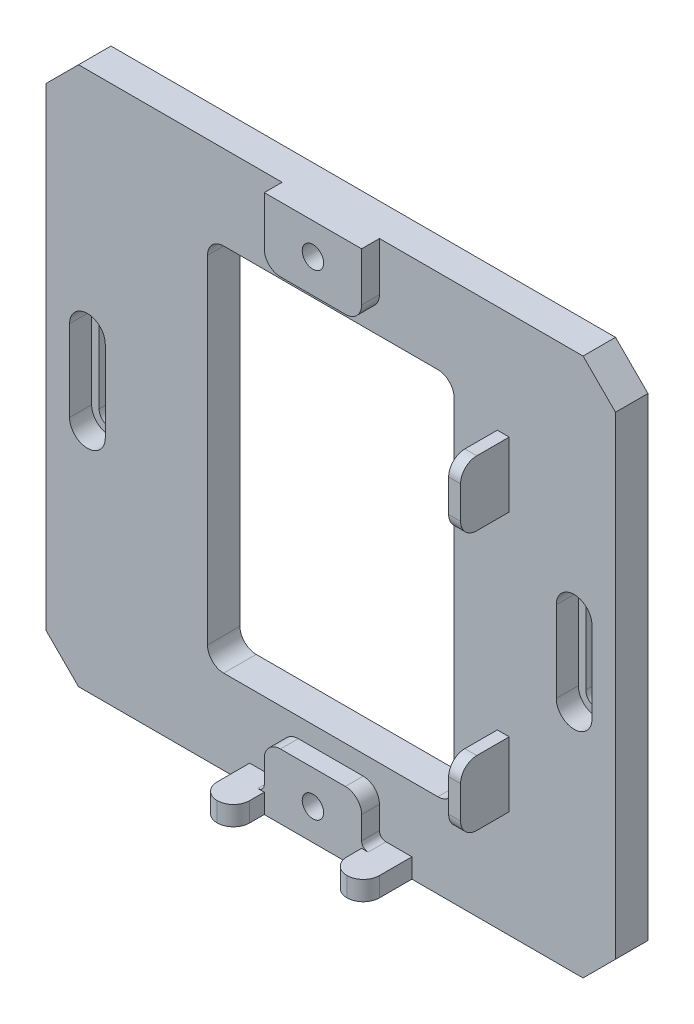
SolidWorks part; units mm, degrees
note: '?' marks a value the reader was unsure of.
material "6061 合金"
ref_plane "前视基准面" through (0, 0, 0) normal (0, 0, 1) x (1, 0, 0)
ref_plane "上视基准面" through (0, 0, 0) normal (0, 1, 0) x (1, 0, 0)
ref_plane "右视基准面" through (0, 0, 0) normal (1, 0, 0) x (0, 0, -1)
sketch "草图1" plane through (0, 0, 0) normal (0, 0, 1) x (1, 0, 0)
  line L0 (0, 0) -> (19.975, 0) construction
  line L1 (0, 0) -> (0, 23.7292) construction
  line L3 (-55, -83) -> (55, -83)
  line L4 (-55, -83) -> (-55, 83)
  line L5 (-55, 83) -> (55, 83)
  line L6 (55, -83) -> (55, 83)
  line L7 (-55, -83) -> (55, 83) construction
  line L8 (-55, 83) -> (55, -83) construction
  dimension "D1" = 110
  dimension "D2" = 166
extrude "凸台-拉伸1" add sketch "草图1" along normal blind 10
sketch "草图2" plane through (0, 0, 10) normal (0, 0, 1) x (1, 0, 0)
  line L0 (0, 0) -> (0, -83) construction
  line L1 (-55, -83) -> (55, -83) construction
  line L2 (0, 0) -> (30.9341, 0) construction
  line L3 (-15, -83) -> (15, -83)
  line L4 (-15, -83) -> (-15, -63)
  line L5 (-15, -63) -> (15, -63)
  line L6 (15, -83) -> (15, -63)
  line L7 (-15, 83) -> (-15, 63)
  line L8 (15, 83) -> (15, 63)
  line L9 (-15, 63) -> (15, 63)
  line L10 (-15, 83) -> (15, 83)
  dimension "D1" = 30
  dimension "D2" = 20
extrude "凸台-拉伸2" add sketch "草图2" along normal blind 5.5
sketch "草图3" plane through (0, 0, 0) normal (0, 0, -1) x (-1, 0, 0)
  line L0 (0, 0) -> (28.9291, 0) construction
  line L1 (0, 0) -> (0, -73.35) construction
  point P0 (0, -73.35)
  point P5 (0, 73.35)
  dimension "D1" = 146.7
hole_wizard "打孔尺寸(%根据)内六角圆柱头螺钉的类型2" positions "草图4" profile "草图5" counterbore size "M6" standard "GB" end condition through all
sketch "草图4" plane through (0, 0, 0) normal (0, 0, -1) x (-1, 0, 0)
  point P0 (0, -73.35)
  point P3 (0, 73.35)
sketch "草图5" plane through (0, -73.35, 0) normal (1, 0, 0) x (0, 1, 0)
  line L0 (0, 0) -> (0, 15.5)
  line L1 (0, 15.5) -> (3.3, 15.5)
  line L3 (3.3, 15.5) -> (3.3, 8.8)
  line L4 (3.3, 8.8) -> (5.5, 8.8)
  line L5 (5.5, 8.8) -> (5.5, 0)
  line L7 (5.5, 0) -> (0, 0)
  line L11 (0, -6.35) -> (0, 107.95) construction
  dimension "通孔孔直径" = 6.6
  dimension "通孔孔深度" = 15.5
  dimension "柱形沉头孔直径" = 11
  dimension "柱形沉头孔深度" = 8.8
sketch "草图6" plane through (0, 0, 10) normal (0, 0, 1) x (1, 0, 0)
  line L0 (-67, 0) -> (67, 0) construction
  line L1 (55, -83) -> (55, 83) construction
  line L2 (79, -10) -> (55, -10)
  line L3 (79, -10) -> (79, 10)
  line L4 (79, 10) -> (55, 10)
  line L5 (55, -10) -> (55, 10)
  line L6 (79, -10) -> (55, 10) construction
  line L7 (79, 10) -> (55, -10) construction
  line L9 (0, 0) -> (0, 19.4942) construction
  line L10 (-79, 10) -> (-55, -10) construction
  line L11 (-79, -10) -> (-55, 10) construction
  line L12 (-55, -10) -> (-55, 10)
  line L13 (-79, 10) -> (-55, 10)
  line L14 (-79, -10) -> (-79, 10)
  line L15 (-79, -10) -> (-55, -10)
  dimension "D1" = 24
  dimension "D2" = 20
extrude "凸台-拉伸3" [suppressed] add sketch "草图6" against normal blind 16.02
hole_wizard "M6 六角头螺钉的柱形沉头孔2" [suppressed] positions "草图7" profile "草图8" counterbore size "M6" standard "ANSI Metric"
sketch "草图7" plane through (0, 0, 10) normal (0, 0, 1) x (1, 0, 0)
  line L0 (0, 0) -> (0, 17.8301) construction
  point P0 (-63, 0)
  point P6 (63, 0)
sketch "草图8" plane through (-63, 0, 10) normal (1, 0, 0) x (0, -1, 0)
  line L0 (0, 0) -> (0, 10)
  line L1 (0, 10) -> (3.3, 10)
  line L3 (3.3, 10) -> (3.3, 4.15)
  line L4 (3.3, 4.15) -> (7.275, 4.15)
  line L5 (7.275, 4.15) -> (7.275, 0)
  line L7 (7.275, 0) -> (0, 0)
  line L11 (0, -6.35) -> (0, 107.95) construction
  dimension "通孔孔直径" = 6.6
  dimension "通孔孔深度" = 10
  dimension "柱形沉头孔直径" = 14.55
  dimension "柱形沉头孔深度" = 4.15
fillet "圆角1" [suppressed] radius 5
fillet "圆角2" radius 15 4 edges at (55, -83, 5) (-55, -83, 5) (55, 83, 5) (-55, 83, 5)
fillet "圆角3" radius 5 4 edges at (-15, 63, 12.75) (15, 63, 12.75) (15, -63, 12.75) (-15, -63, 12.75)
sketch "草图9" plane through (0, 0, 10) normal (0, 0, 1) x (1, 0, 0)
  line L1 (-38, -57) -> (38, -57)
  line L2 (-38, -57) -> (-38, 57)
  line L3 (-38, 57) -> (38, 57)
  line L4 (38, -57) -> (38, 57)
  line L5 (-38, -57) -> (38, 57) construction
  line L6 (-38, 57) -> (38, -57) construction
  point P0 (0, 0)
  dimension "D1" = 114
  dimension "D2" = 76
extrude "切除-拉伸1" cut sketch "草图9" against normal through all
fillet "圆角4" radius 5 4 edges at (38, -57, 5) (-38, -57, 5) (38, 57, 5) (-38, 57, 5)
sketch "草图10" plane through (0, 0, 0) normal (0, 0, -1) x (-1, 0, 0)
  line L0 (0, 0) -> (-90.6559, 0) construction
  line L1 (47, 0) -> (49, 0) construction
  line L2 (47, 2) -> (49, 2)
  line L3 (47, -2) -> (49, -2)
  line L4 (0, 0) -> (0, -73.35) construction
  circle A0 centre (-48, 0) radius 2
  arc A1 (47, 2) -> (47, -2) centre (47, 0) ccw
  arc A2 (49, -2) -> (49, 2) centre (49, 0) ccw
  point P7 (48, 0)
  dimension "D1" = 4
  dimension "D5" = 48
  dimension "D2" = 4
  dimension "D3" = 2
  dimension "D4" = 96
extrude "切除-拉伸2" [suppressed] cut sketch "草图10" against normal blind 6
sketch "草图11" plane through (0, 0, 10) normal (0, 0, 1) x (1, 0, 0)
  line L0 (-75.7527, 0) -> (-87.7527, 0) construction
  line L5 (0, 0) -> (-75.7527, 0) construction
  line L7 (0, -73.35) -> (0, 0) construction
  line L8 (87.7527, 0) -> (87.7527, 20) construction
  line L9 (75.7527, 0) -> (87.7527, 0) construction
  line L18 (-87.7527, 0) -> (-87.7527, 20) construction
  line L34 (-55, 68) -> (-55, -68) construction
  line L35 (-87.7527, 20) -> (-55, 20)
  line L36 (-87.7527, 20) -> (-87.7527, -20)
  line L37 (-87.7527, -20) -> (-55, -20)
  line L38 (-55, 20) -> (-55, -20)
  line L40 (55, 20) -> (55, -20)
  line L41 (87.7527, -20) -> (55, -20)
  line L42 (87.7527, 20) -> (87.7527, -20)
  line L43 (87.7527, 20) -> (55, 20)
  dimension "D1" = 12
  dimension "D2" = 20
  dimension "D3" = 40
extrude "凸台-拉伸4" add sketch "草图11" against normal up to surface (10 mm away) up to face at (0, 0, 0)
sketch "草图12" plane through (0, 0, 10) normal (0, 0, 1) x (1, 0, 0)
  line L0 (0, 0) -> (-75, 0) construction
  line L3 (-75, 12.5) -> (-75, -12.5) construction
  line L4 (0, 0) -> (0, -73.35) construction
  line L5 (75, 12.5) -> (75, -12.5) construction
  circle A0 centre (-75, 0) radius 3.6475
  circle A1 centre (75, 0) radius 3.4956
  point P3 (-75, 0)
  point P7 (75, 0)
  dimension "D1" = 75
  dimension "D2" = 25
ref_axis "基准轴1" [suppressed] through (0, 0, 16.02) along (0, -1, 0)?
hole_wizard "打孔尺寸(%根据)内六角圆柱头螺钉的类型2" positions "3D草图1" profile "草图13" counterbore size "M6" standard "GB" end condition through all
sketch3d "3D草图1"
  point P14 (-121.4422, 88.7703, 0)
  point P22 (-75, 12.5, 10)
  point P25 (-75, -12.5, 10)
  point P28 (75, 12.5, 10)
  point P31 (75, -12.5, 10)
sketch "草图13" plane through (75, -12.5, 10) normal (1, 0, 0) x (0, -1, 0)
  line L0 (0, 0) -> (0, 10)
  line L1 (0, 10) -> (3.2, 10)
  line L3 (3.2, 10) -> (3.2, 6.8)
  line L4 (3.2, 6.8) -> (5.5, 6.8)
  line L5 (5.5, 6.8) -> (5.5, 0)
  line L7 (5.5, 0) -> (0, 0)
  line L11 (0, -6.35) -> (0, 107.95) construction
  dimension "通孔孔直径" = 6.4
  dimension "通孔孔深度" = 10
  dimension "柱形沉头孔直径" = 11
  dimension "柱形沉头孔深度" = 6.8
sketch "草图14" plane through (0, 0, 10) normal (0, 0, 1) x (1, 0, 0)
  line L5 (-80.5, 12.5) -> (-69.5, 12.5)
  line L6 (-80.5, 12.5) -> (-80.5, -12.5)
  line L7 (-80.5, -12.5) -> (-69.5, -12.5)
  line L8 (-69.5, 12.5) -> (-69.5, -12.5)
  line L9 (69.5, 12.5) -> (80.5, 12.5)
  line L10 (69.5, 12.5) -> (69.5, -12.5)
  line L11 (69.5, -12.5) -> (80.5, -12.5)
  line L12 (80.5, 12.5) -> (80.5, -12.5)
  circle A4 centre (-75, 12.5) radius 5.5 construction
  circle A5 centre (-75, 12.5) radius 5.5 construction
  circle A6 centre (-75, -12.5) radius 5.5 construction
  circle A7 centre (-75, -12.5) radius 5.5 construction
  circle A8 centre (75, 12.5) radius 5.5 construction
  circle A9 centre (75, 12.5) radius 5.5 construction
  circle A10 centre (75, -12.5) radius 5.5 construction
  circle A11 centre (75, -12.5) radius 5.5 construction
extrude "切除-拉伸3" cut sketch "草图14" against normal up to surface (6.8 mm away) up to face at (-71.8, 12.5, 3.2)
fillet "圆角5" radius 5 8 edges at (55, 20, 5) (87.7527, 20, 5) (87.7527, -20, 5) (55, -20, 5) (-55, -20, 5) (-87.7527, -20, 5) (-87.7527, 20, 5) (-55, 20, 5)
ref_plane "基准面1" through (0, 0, 0) normal (-1, 0, 0) x (0, -1, 0)
sketch "草图16" plane through (0, 0, 3.2) normal (0, 0, 1) x (1, 0, 0)
  line L1 (-78.2, 12.5) -> (-71.8, 12.5)
  line L2 (-78.2, 12.5) -> (-78.2, -12.5)
  line L3 (-78.2, -12.5) -> (-71.8, -12.5)
  line L4 (-71.8, 12.5) -> (-71.8, -12.5)
  line L5 (71.8, 12.5) -> (78.2, 12.5)
  line L6 (71.8, 12.5) -> (71.8, -12.5)
  line L7 (71.8, -12.5) -> (78.2, -12.5)
  line L8 (78.2, 12.5) -> (78.2, -12.5)
  circle A0 centre (-75, 12.5) radius 3.2 construction
  circle A1 centre (-75, -12.5) radius 3.2 construction
  circle A2 centre (75, 12.5) radius 3.2 construction
  circle A3 centre (75, -12.5) radius 3.2 construction
extrude "切除-拉伸5" cut sketch "草图16" against normal through all
sketch "草图17" plane through (0, -83, 0) normal (0, 1, 0) x (1, 0, 0)
  line L1 (-15, -10) -> (-25, -10)
  line L2 (-15, -10) -> (-15, -25)
  line L3 (-15, -25) -> (-25, -25)
  line L4 (-25, -10) -> (-25, -25)
  line L5 (15, -10) -> (25, -10)
  line L6 (15, -10) -> (15, -25)
  line L7 (15, -25) -> (25, -25)
  line L8 (25, -10) -> (25, -25)
  dimension "D1" = 10
  dimension "D2" = 15
extrude "凸台-拉伸5" add sketch "草图17" along normal up to surface (5.972 mm away)
sketch "草图18" plane through (55, 0, 0) normal (1, 0, 0) x (0, 0, -1)
  line L0 (-10, 30) -> (-10, -30) construction
  line L2 (-10, 0) -> (-10, -73.35) construction
  line L4 (-10, 30) -> (-25, 30)
  line L5 (-10, 30) -> (-10, 50)
  line L6 (-10, 50) -> (-25, 50)
  line L7 (-25, 30) -> (-25, 50)
  line L8 (-10, -30) -> (-25, -30)
  line L9 (-10, -30) -> (-10, -50)
  line L10 (-10, -50) -> (-25, -50)
  line L11 (-25, -30) -> (-25, -50)
  point P4 (-10, 0)
  dimension "D1" = 60
  dimension "D2" = 15
  dimension "D3" = 20
extrude "凸台-拉伸6" add sketch "草图18" along normal up to surface (3.675 mm away)
fillet "圆角6" radius 5 8 edges at (53.1625, 50, 25) (53.1625, 30, 25) (53.1625, -30, 25) (53.1625, -50, 25) (25, -80.014, 25) (15, -80.014, 25) (-15, -80.014, 25) (-25, -80.014, 25)
fillet "圆角7" radius 2 2 edges at (15, -77.028, 12.75) (-15, -77.028, 12.75)
sketch "草图19" plane through (0, 0, 0) normal (0, 0, -1) x (-1, 0, 0)
  line L0 (-75, 0) -> (-65, 0) construction
  line L1 (75, 0) -> (65, 0) construction
  line L2 (0, 0) -> (75, 0) construction
  dimension "D1" = 10
  dimension "D2" = 10
hole_wizard "大小mm 暗销孔1" positions "3D草图2" profile "草图20" hole size "Ø4.0" standard "GB"
sketch3d "3D草图2"
  point P0 (65, 0, 0)
sketch "草图20" plane through (65, 0, 0) normal (1, 0, 0) x (0, 1, 0)
  line L0 (0, 0) -> (0, 6.2017)
  line L1 (0, 6.2017) -> (2, 5)
  line L2 (2, 5) -> (2, 0)
  line L5 (2, 0) -> (0, 0)
  line L10 (0, 6.2017) -> (-2, 5) construction
  line L11 (0, -6.35) -> (0, 107.95) construction
  dimension "孔直径" = 4
  dimension "孔深度" = 5
  dimension "导头角度" = 118
sketch "草图21" plane through (0, 0, 0) normal (0, 0, -1) x (-1, 0, 0)
  line L0 (65.5, 0) -> (64.5, 0) construction
  line L1 (0, 0) -> (75, 0) construction
  line L2 (65.5, -2) -> (64.5, -2)
  line L3 (65.5, 2) -> (64.5, 2)
  arc A0 (65.5, -2) -> (65.5, 2) centre (65.5, 0) ccw
  arc A1 (64.5, 2) -> (64.5, -2) centre (64.5, 0) ccw
  point P5 (65, 0)
  dimension "D1" = 2
  dimension "D2" = 1
extrude "切除-拉伸6" cut sketch "草图21" against normal blind 5
sketch "草图22" plane through (0, 0, 0) normal (0, 0, -1) x (-1, 0, 0)
  circle A0 centre (-65, 0) radius 2
  circle A1 centre (65, 0) radius 2
sketch "草图23" plane through (0, 0, 10) normal (0, 0, 1) x (1, 0, 0)
  line L1 (-87.7527, 83) -> (87.7527, 83)
  line L2 (-87.7527, 83) -> (-87.7527, -83)
  line L3 (-87.7527, -83) -> (87.7527, -83)
  line L4 (87.7527, 83) -> (87.7527, -83)
  line L32 (15, -68) -> (15, -75.028)
  line L33 (17, -77.028) -> (25, -77.028)
  line L34 (25, -77.028) -> (25, -83)
  line L35 (25, -83) -> (40, -83)
  line L36 (55, -68) -> (55, -50)
  line L37 (55, -50) -> (51.325, -50)
  line L38 (51.325, -50) -> (51.325, -30)
  line L39 (51.325, -30) -> (55, -30)
  line L40 (55, -30) -> (55, -25)
  line L41 (60, -20) -> (82.7527, -20)
  line L42 (87.7527, -15) -> (87.7527, 15)
  line L43 (82.7527, 20) -> (60, 20)
  line L44 (55, 25) -> (55, 30)
  line L45 (55, 30) -> (51.325, 30)
  line L46 (51.325, 30) -> (51.325, 50)
  line L47 (51.325, 50) -> (55, 50)
  line L48 (55, 50) -> (55, 68)
  line L49 (40, 83) -> (15, 83)
  line L50 (15, 83) -> (15, 68)
  line L51 (10, 63) -> (-10, 63)
  line L52 (-15, 68) -> (-15, 83)
  line L53 (-15, 83) -> (-40, 83)
  line L54 (-55, 68) -> (-55, 25)
  line L55 (-60, 20) -> (-82.7527, 20)
  line L56 (-87.7527, 15) -> (-87.7527, -15)
  line L57 (-82.7527, -20) -> (-60, -20)
  line L58 (-55, -25) -> (-55, -68)
  line L59 (-40, -83) -> (-25, -83)
  line L60 (-25, -83) -> (-25, -77.028)
  line L61 (-25, -77.028) -> (-17, -77.028)
  line L62 (-15, -75.028) -> (-15, -68)
  line L63 (-10, -63) -> (10, -63)
  line L64 (15, -68) -> (15, -75.028)
  line L65 (17, -77.028) -> (25, -77.028)
  line L66 (25, -77.028) -> (25, -83)
  line L67 (25, -83) -> (40, -83)
  line L68 (55, -68) -> (55, -50)
  line L69 (55, -50) -> (51.325, -50)
  line L70 (51.325, -50) -> (51.325, -30)
  line L71 (51.325, -30) -> (55, -30)
  line L72 (55, -30) -> (55, -25)
  line L73 (60, -20) -> (82.7527, -20)
  line L74 (87.7527, -15) -> (87.7527, 15)
  line L75 (82.7527, 20) -> (60, 20)
  line L76 (55, 25) -> (55, 30)
  line L77 (55, 30) -> (51.325, 30)
  line L78 (51.325, 30) -> (51.325, 50)
  line L79 (51.325, 50) -> (55, 50)
  line L80 (55, 50) -> (55, 68)
  line L81 (40, 83) -> (15, 83)
  line L82 (15, 83) -> (15, 68)
  line L83 (10, 63) -> (-10, 63)
  line L84 (-15, 68) -> (-15, 83)
  line L85 (-15, 83) -> (-40, 83)
  line L86 (-55, 68) -> (-55, 25)
  line L87 (-60, 20) -> (-82.7527, 20)
  line L88 (-87.7527, 15) -> (-87.7527, -15)
  line L89 (-82.7527, -20) -> (-60, -20)
  line L90 (-55, -25) -> (-55, -68)
  line L91 (-40, -83) -> (-25, -83)
  line L92 (-25, -83) -> (-25, -77.028)
  line L93 (-25, -77.028) -> (-17, -77.028)
  line L94 (-15, -75.028) -> (-15, -68)
  line L95 (-10, -63) -> (10, -63)
  arc A18 (15, -75.028) -> (17, -77.028) centre (17, -75.028) ccw
  arc A19 (40, -83) -> (55, -68) centre (40, -68) ccw
  arc A20 (60, -20) -> (55, -25) centre (60, -25) ccw
  arc A21 (82.7527, -20) -> (87.7527, -15) centre (82.7527, -15) ccw
  arc A22 (87.7527, 15) -> (82.7527, 20) centre (82.7527, 15) ccw
  arc A23 (55, 25) -> (60, 20) centre (60, 25) ccw
  arc A24 (55, 68) -> (40, 83) centre (40, 68) ccw
  arc A25 (10, 63) -> (15, 68) centre (10, 68) ccw
  arc A26 (-15, 68) -> (-10, 63) centre (-10, 68) ccw
  arc A27 (-40, 83) -> (-55, 68) centre (-40, 68) ccw
  arc A28 (-60, 20) -> (-55, 25) centre (-60, 25) ccw
  arc A29 (-82.7527, 20) -> (-87.7527, 15) centre (-82.7527, 15) ccw
  arc A30 (-87.7527, -15) -> (-82.7527, -20) centre (-82.7527, -15) ccw
  arc A31 (-55, -25) -> (-60, -20) centre (-60, -25) ccw
  arc A32 (-55, -68) -> (-40, -83) centre (-40, -68) ccw
  arc A33 (-17, -77.028) -> (-15, -75.028) centre (-17, -75.028) ccw
  arc A34 (-10, -63) -> (-15, -68) centre (-10, -68) ccw
  arc A35 (15, -68) -> (10, -63) centre (10, -68) ccw
  arc A36 (15, -75.028) -> (17, -77.028) centre (17, -75.028) ccw
  arc A37 (40, -83) -> (55, -68) centre (40, -68) ccw
  arc A38 (60, -20) -> (55, -25) centre (60, -25) ccw
  arc A39 (82.7527, -20) -> (87.7527, -15) centre (82.7527, -15) ccw
  arc A40 (87.7527, 15) -> (82.7527, 20) centre (82.7527, 15) ccw
  arc A41 (55, 25) -> (60, 20) centre (60, 25) ccw
  arc A42 (55, 68) -> (40, 83) centre (40, 68) ccw
  arc A43 (10, 63) -> (15, 68) centre (10, 68) ccw
  arc A44 (-15, 68) -> (-10, 63) centre (-10, 68) ccw
  arc A45 (-40, 83) -> (-55, 68) centre (-40, 68) ccw
  arc A46 (-60, 20) -> (-55, 25) centre (-60, 25) ccw
  arc A47 (-82.7527, 20) -> (-87.7527, 15) centre (-82.7527, 15) ccw
  arc A48 (-87.7527, -15) -> (-82.7527, -20) centre (-82.7527, -15) ccw
  arc A49 (-55, -25) -> (-60, -20) centre (-60, -25) ccw
  arc A50 (-55, -68) -> (-40, -83) centre (-40, -68) ccw
  arc A51 (-17, -77.028) -> (-15, -75.028) centre (-17, -75.028) ccw
  arc A52 (-10, -63) -> (-15, -68) centre (-10, -68) ccw
  arc A53 (15, -68) -> (10, -63) centre (10, -68) ccw
  dimension "D1" = 0
extrude "凸台-拉伸7" add sketch "草图23" against normal up to surface (10 mm away) contours A47 L87 A46 L86 A45 L1 L2 | A50 L90 A49 L89 A48 L2 L3 | A39 L73 A38 L72 L71 L70 L69 L68 A37 L3 L4 | A42 L80 L79 L78 L77 L76 A41 L75 A40 L4 L1 up to face at (-65, 0, 0)
chamfer "倒角1" distance 10 angle 45 4 edges at (87.7527, 83, 5) (87.7527, -83, 5) (-87.7527, -83, 5) (-87.7527, 83, 5)
